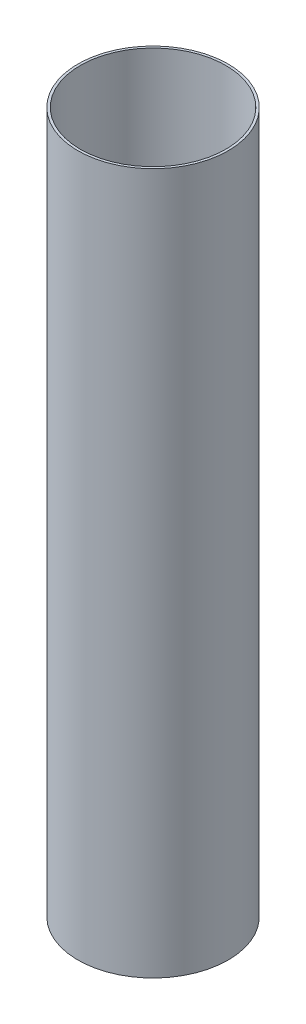
SolidWorks part; units mm, degrees
material "6061-T6 (SS)"
ref_plane "Front Plane" through (0, 0, 0) normal (0, 0, 1) x (1, 0, 0)
ref_plane "Top Plane" through (0, 0, 0) normal (0, 1, 0) x (1, 0, 0)
ref_plane "Right Plane" through (0, 0, 0) normal (1, 0, 0) x (0, 0, -1)
sketch "Sketch1" plane through (0, 0, 0) normal (0, 1, 0) x (1, 0, 0)
  circle A0 centre (0, 0) radius 98.425
  dimension "D1" = 196.85
extrude "Extrude-Thin1" add sketch "Sketch1" along normal blind 948.69 thin thin type one direction wall 3.302
